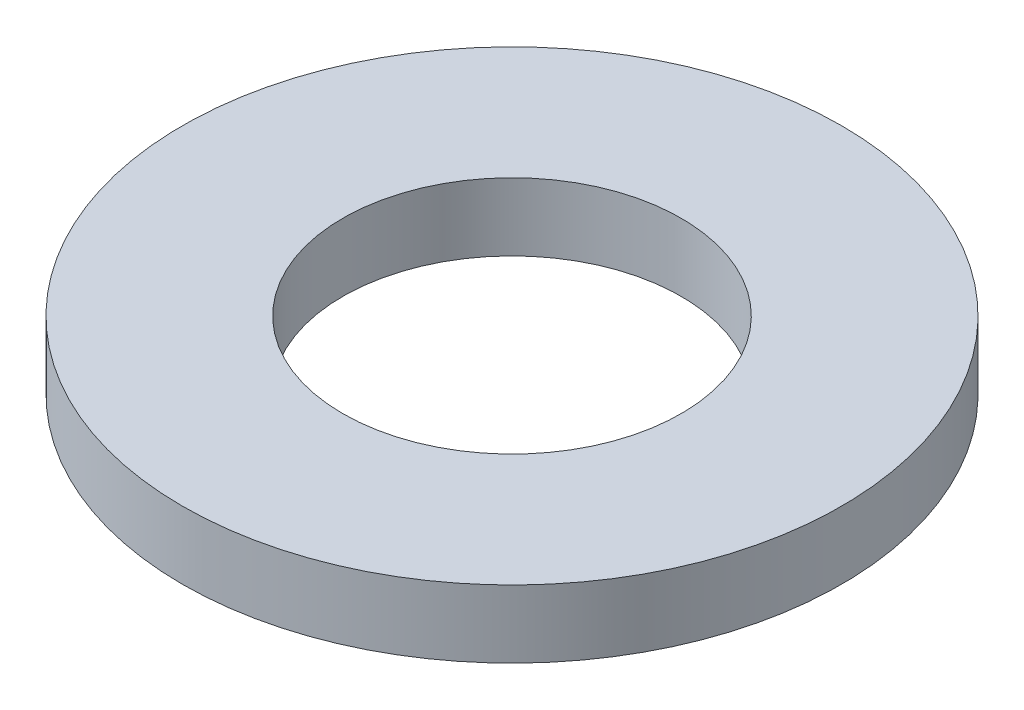
SolidWorks part; units mm, degrees
ref_plane "Front Plane" through (0, 0, 0) normal (0, 0, 1) x (1, 0, 0)
ref_plane "Top Plane" through (0, 0, 0) normal (0, 1, 0) x (1, 0, 0)
ref_plane "Right Plane" through (0, 0, 0) normal (1, 0, 0) x (0, 0, -1)
sketch "Sketch1" plane through (0, 0, 0) normal (0, 1, 0) x (1, 0, 0)
  circle A0 centre (0, 0) radius 92.5
  dimension "FLANGE_OD" = 185
extrude "Boss-Extrude1" add sketch "Sketch1" along normal blind 19
sketch "Sketch2" plane through (0, 0, 0) normal (0, 1, 0) x (1, 0, 0)
  circle A0 centre (0, 0) radius 47.5
  dimension "BORE_D" = 95
extrude "Cut-Extrude1" cut sketch "Sketch2" along normal through all
sketch "Sketch3" plane through (0, 19, 0) normal (0, 1, 0) x (1, 0, 0)
  circle A0 centre (0, 0) radius 33.8896 construction
  circle A1 centre (-33.8896, 0) radius 1.9953
  dimension "BOLT_D" = 3.9905
  dimension "BOLT_PCD" = 67.7791
extrude "Cut-Extrude2" cut sketch "Sketch3" against normal blind 13.9691 rebuild error yes
pattern_circular "CirPattern1" count 4 over 360 rebuild error yes
